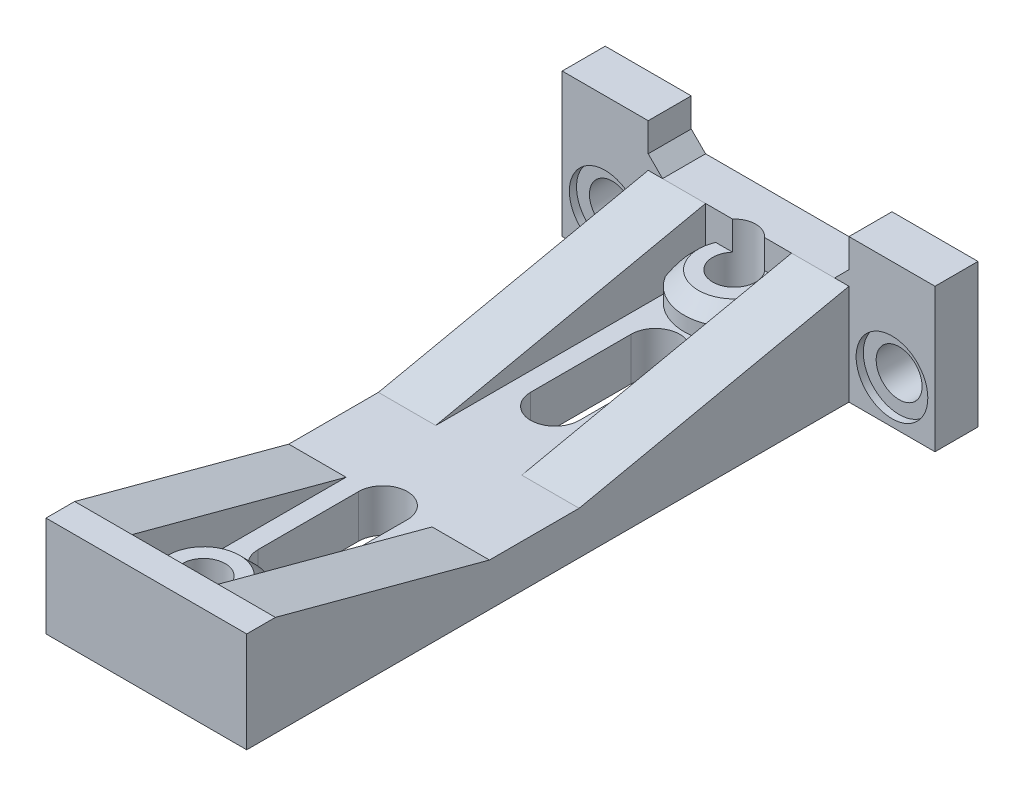
SolidWorks part; units mm, degrees
ref_plane "前视基准面" through (0, 0, 0) normal (0, 0, 1) x (1, 0, 0)
ref_plane "上视基准面" through (0, 0, 0) normal (0, 1, 0) x (1, 0, 0)
ref_plane "右视基准面" through (0, 0, 0) normal (1, 0, 0) x (0, 0, -1)
sketch "草图1" plane through (0, 0, 0) normal (0, 1, 0) x (1, 0, 0)
  line L0 (0, 0) -> (0, -45)
  line L1 (0, 0) -> (14, 0)
  line L2 (14, 0) -> (14, -45)
  line L3 (14, -45) -> (0, -45)
  dimension "D1" = 45
  dimension "D2" = 14
extrude "凸台-拉伸1" add sketch "草图1" along normal blind 3
sketch "草图4" plane through (0, 0, 0) normal (0, -1, 0) x (1, 0, 0)
  line L0 (14, 45) -> (14, 0) construction
  line L1 (14, 3) -> (20, 3)
  line L2 (14, 3) -> (14, 0)
  line L3 (14, 0) -> (20, 0)
  line L4 (20, 3) -> (20, 0)
  dimension "D1" = 6
  dimension "D2" = 3
extrude "凸台-拉伸2" add sketch "草图4" against normal blind 10
ref_plane "基准面1" through (7, 0, 0) normal (1, 0, 0) x (0, 0, -1)
sketch "草图5" plane through (0, 0, 3) normal (0, 0, 1) x (1, 0, 0)
  line L0 (17, 10) -> (17, 0) construction
  line L1 (20, 10) -> (14, 10) construction
  line L2 (20, 0) -> (14, 0) construction
  circle A0 centre (17, 3) radius 1.5
  dimension "D1" = 3
  dimension "D2" = 3
hole_wizard "M3 六角头螺栓的柱形沉头孔1" positions "草图8" profile "草图9" counterbore size "M3" standard "GB"
sketch "草图8" plane through (0, 0, 3) normal (0, 0, 1) x (1, 0, 0)
  point P0 (17, 3)
sketch "草图9" plane through (17, 3, 3) normal (1, 0, 0) x (0, -1, 0)
  line L0 (0, 0) -> (0, 5.9614)
  line L1 (0, 5.9614) -> (1.6, 5)
  line L2 (1.6, 5) -> (1.6, 0.5)
  line L3 (1.6, 0.5) -> (2.5, 0.5)
  line L4 (2.5, 0.5) -> (2.5, 0)
  line L5 (2.5, 0) -> (0, 0)
  line L10 (0, 5.9614) -> (-1.6, 5) construction
  line L11 (0, -6.35) -> (0, 107.95) construction
  dimension "孔直径" = 3.2
  dimension "孔深度" = 5
  dimension "柱形沉头孔直径" = 5
  dimension "柱形沉头孔深度" = 0.5
  dimension "导头角度" = 118
mirror "镜向1" about plane through (7, 0, 0) normal (1, 0, 0) of "M3 六角头螺栓的柱形沉头孔1", "凸台-拉伸2"
sketch "草图10" plane through (14, 0, 0) normal (-1, 0, 0) x (0, 0, 1)
  line L0 (0, 10) -> (0, 3) construction
  line L1 (0, 7) -> (3, 7)
  line L2 (0, 7) -> (0, 3)
  line L3 (0, 3) -> (3, 3)
  line L4 (3, 7) -> (3, 3)
  dimension "D1" = 4
extrude "凸台-拉伸3" add sketch "草图10" along normal up to surface (14 mm away) up to face at (0, 6.5, 1.5)
sketch "草图2" plane through (0, 0, 0) normal (0, -1, 0) x (1, 0, 0)
  line L0 (7, 45) -> (7, 0) construction
  line L1 (0, 45) -> (14, 45) construction
  line L2 (20, 0) -> (-6, 0) construction
  line L3 (7, 22.5) -> (0, 22.5) construction
  circle A0 centre (7, 41) radius 1.5
  circle A1 centre (7, 4) radius 1.5
  dimension "D1" = 3
  dimension "D2" = 37
extrude "切除-拉伸1" cut sketch "草图2" against normal through all and the other way through all
sketch "草图11" plane through (14, 0, 0) normal (1, 0, 0) x (0, 0, -1)
  line L0 (-3, 7) -> (-21.8185, 3)
  line L1 (-3, 10) -> (-3, 7) construction
  line L2 (-45, 3) -> (-3, 3) construction
  dimension "D1" = 4
  dimension "D2" = 12
rib "筋8" sketch "草图11" sketch "草图11" thickness 4 extrusion direction parallel to sketch draft on no parameters "D1"=4
sketch "草图3" plane through (0, 3, 0) normal (0, 1, 0) x (1, 0, 0)
  circle A0 centre (7, -41) radius 1.5 construction
  circle A1 centre (7, -4) radius 1.5 construction
  circle A2 centre (7, -41) radius 1.5
  circle A3 centre (7, -4) radius 1.5
extrude "拉伸-薄壁1" add sketch "草图3" along normal blind 2 thin thin type one direction wall 2
sketch "草图12" plane through (0, 3, 0) normal (0, 1, 0) x (1, 0, 0)
  line L0 (0, -3) -> (0, -45) construction
  line L1 (0, -43) -> (14, -43)
  line L2 (0, -43) -> (0, -45)
  line L3 (0, -45) -> (14, -45)
  line L4 (14, -43) -> (14, -45)
  dimension "D1" = 2
extrude "凸台-拉伸4" add sketch "草图12" along normal blind 4
sketch "草图13" plane through (14, 0, 0) normal (1, 0, 0) x (0, 0, -1)
  line L0 (-43, 7) -> (-28.0718, 3)
  line L1 (-43, 3) -> (-21.8185, 3) construction
  dimension "D1" = 15
rib "筋9" sketch "草图13" sketch "草图13" thickness 4 extrusion direction parallel to sketch draft on no parameters "D1"=4
mirror "镜向2" about plane through (7, 0, 0) normal (1, 0, 0) of "筋8", "筋9"
chamfer "倒角1" distance 1 angle 45 2 edges at (7, 5, 7.5) (7, 5, 37.5) tangent propagation no
sketch "草图14" plane through (0, 0, 0) normal (0, -1, 0) x (1, 0, 0)
  line L0 (7, 45) -> (7, 0) construction
  line L1 (0, 45) -> (14, 45) construction
  line L2 (20, 0) -> (-6, 0) construction
  line L3 (7, 35.5) -> (7, 28.5) construction
  line L4 (8.7, 35.5) -> (8.7, 28.5)
  line L5 (5.3, 35.5) -> (5.3, 28.5)
  line L6 (7, 22.5) -> (14, 22.5) construction
  line L7 (14, 45) -> (14, 3) construction
  line L8 (7, 9.5) -> (7, 16.5) construction
  line L9 (8.7, 9.5) -> (8.7, 16.5)
  line L10 (5.3, 9.5) -> (5.3, 16.5)
  arc A0 (8.7, 35.5) -> (5.3, 35.5) centre (7, 35.5) ccw
  arc A1 (5.3, 28.5) -> (8.7, 28.5) centre (7, 28.5) ccw
  arc A2 (8.7, 9.5) -> (5.3, 9.5) centre (7, 9.5) cw
  arc A3 (5.3, 16.5) -> (8.7, 16.5) centre (7, 16.5) cw
  point P8 (7, 32)
  point P19 (7, 13)
  dimension "D1" = 1.7
  dimension "D3" = 12
  dimension "D2" = 7
extrude "切除-拉伸2" cut sketch "草图14" against normal blind 4
chamfer "倒角2" distance 1 angle 45 2 edges at (0, 7, 1.5) (14, 7, 1.5)
